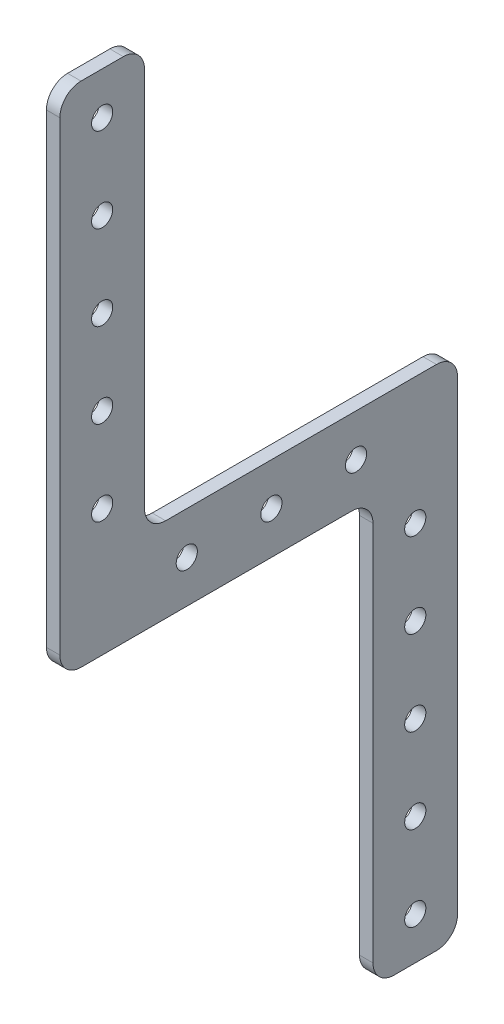
SolidWorks part; units mm, degrees
ref_plane "Front Plane" through (0, 0, 0) normal (0, 0, 1) x (1, 0, 0)
ref_plane "Top Plane" through (0, 0, 0) normal (0, 1, 0) x (1, 0, 0)
ref_plane "Right Plane" through (0, 0, 0) normal (1, 0, 0) x (0, 0, -1)
sketch "Sketch2" plane through (0, 0, 0) normal (1, 0, 0) x (0, 0, -1)
  line L0 (-47, 110) -> (-27, 110)
  line L1 (-27, 110) -> (-27, 10)
  line L2 (-27, 10) -> (47, 10)
  line L3 (47, 10) -> (47, -110)
  line L4 (47, -110) -> (27, -110)
  line L5 (27, -110) -> (27, -10)
  line L6 (27, -10) -> (-47, -10)
  line L7 (-47, -10) -> (-47, 110)
  line L8 (-37, 100) -> (-37, 80) construction
  line L9 (37, -100) -> (37, -80) construction
  line L10 (-17, 0) -> (3, 0) construction
  circle A0 centre (-37, 100) radius 2.5
  circle A1 centre (-37, 80) radius 2.5
  circle A2 centre (-37, 60) radius 2.5
  circle A3 centre (-37, 40) radius 2.5
  circle A4 centre (-37, 20) radius 2.5
  circle A6 centre (37, -100) radius 2.5
  circle A7 centre (37, -80) radius 2.5
  circle A8 centre (37, -60) radius 2.5
  circle A9 centre (37, -40) radius 2.5
  circle A10 centre (37, -20) radius 2.5
  circle A13 centre (-17, 0) radius 2.5
  circle A14 centre (3, 0) radius 2.5
  circle A15 centre (23, 0) radius 2.5
  point P25 (37, -110)
  dimension "D9" = 5
  dimension "D1" = 20
  dimension "D2" = 20
  dimension "D3" = 120
  dimension "D4" = 94
  dimension "D5" = 47
  dimension "D6" = 10
  dimension "D7" = 10
  dimension "D8" = 10
  dimension "D11" = 20
  dimension "D12" = 10
  dimension "D14" = 20
  dimension "D15" = 10
  dimension "D17" = 20
  dimension "D10" = 5
  dimension "D13" = 5
  dimension "D16" = 3
extrude "Boss-Extrude1" add sketch "Sketch2" along normal blind 3.175
fillet "Fillet1" radius 5 8 edges at (1.5875, -110, -47) (1.5875, -110, -27) (1.5875, -10, -27) (1.5875, 10, -47) (1.5875, 10, 27) (1.5875, -10, 47) (1.5875, 110, 27) (1.5875, 110, 47)
equation "\"D2@Sketch2\"=\"D1@Sketch2\""
equation "\"D5@Sketch2\"=\"D4@Sketch2\"/2"
